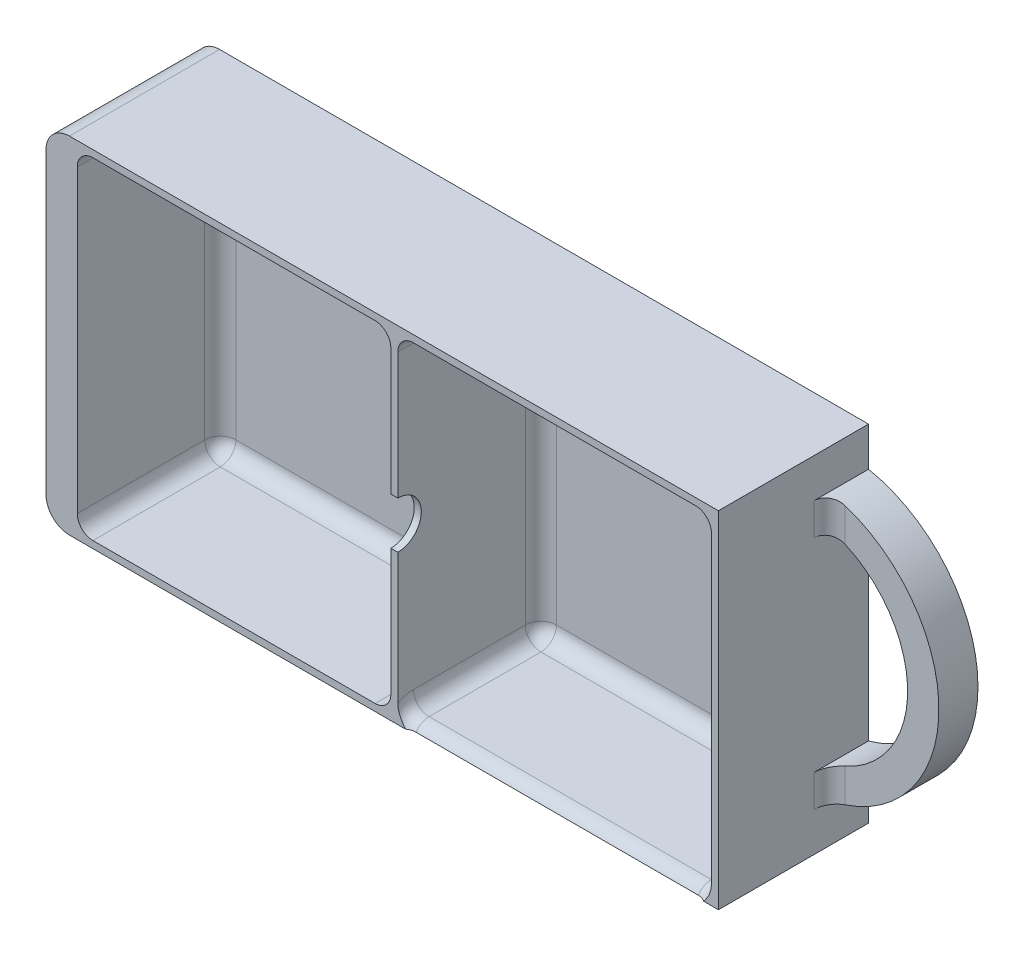
SolidWorks part; units mm, degrees
ref_plane "Спереди" through (0, 0, 0) normal (0, 0, 1) x (1, 0, 0)
ref_plane "Сверху" through (0, 0, 0) normal (0, 1, 0) x (1, 0, 0)
ref_plane "Справа" through (0, 0, 0) normal (1, 0, 0) x (0, 0, -1)
ref_plane "Плоскость4" through (0, 0, 9.6) normal (0, 0, 1) x (1, 0, 0)
sketch "Эскиз1" plane through (0, 0, 9.6) normal (0, 0, 1) x (1, 0, 0)
  line L0 (90, -22.1) -> (90, 22.1)
  line L1 (90, 22.1) -> (4, 22.1)
  line L2 (4, 22.1) -> (4, -22.1)
  line L3 (4, -22.1) -> (90, -22.1)
extrude "Бобышка-Вытянуть1" add sketch "Эскиз1" against normal blind 14.2
sketch "Эскиз2" plane through (0, 0, -4.6) normal (0, 0, -1) x (-1, 0, 0)
  line L0 (-90, -22.1) -> (-90, -17.1)
  line L1 (-90, 17.1) -> (-90, 22.1)
  line L2 (-90, 22.1) -> (-4, 22.1)
  line L3 (-4, 22.1) -> (-4, -22.1)
  line L4 (-4, -22.1) -> (-90, -22.1)
  line L5 (-90, -12.9948) -> (-90, 12.9948)
  arc A0 (-90, -17.1) -> (-90, 17.1) centre (-86.5568, 0) cw
  arc A1 (-90, 12.9948) -> (-90, -12.9948) centre (-86.5568, 0) ccw
extrude "Бобышка-Вытянуть2" add sketch "Эскиз2" along normal blind 5
sketch "Эскиз3" plane through (0, 0, 9.6) normal (0, 0, 1) x (1, 0, 0)
  line L0 (48.1, -21.2) -> (48.1, 21.2)
  line L1 (48.1, 21.2) -> (8, 21.2)
  line L2 (8, 21.2) -> (8, -21.2)
  line L3 (8, -21.2) -> (48.1, -21.2)
extrude "Вырез-Вытянуть1" cut sketch "Эскиз3" against normal blind 18.3
sketch "Эскиз4" plane through (0, 0, 9.6) normal (0, 0, 1) x (1, 0, 0)
  line L0 (49, 21.2) -> (49, -21.2)
  line L1 (49, -21.2) -> (89.1, -21.2)
  line L2 (89.1, -21.2) -> (89.1, 21.2)
  line L3 (89.1, 21.2) -> (49, 21.2)
extrude "Вырез-Вытянуть2" cut sketch "Эскиз4" against normal blind 18.3
hole_wizard "Диаметр отверстия Ø8.3 (8.3)1" positions "Эскиз6" profile "Эскиз5" hole size "Ø8.3" standard "Ansi Metric"
sketch "Эскиз6" plane through (4, 0, 0) normal (-1, 0, 0) x (0, 0, 1)
  point P0 (0, 0)
sketch "Эскиз5" plane through (4, 0, 0) normal (0, 1, 0) x (0, 0, 1)
  line L0 (0, 0) -> (0, 3.2)
  line L1 (0, 3.2) -> (4.15, 3.2)
  line L2 (4.15, 3.2) -> (4.15, 0)
  line L5 (4.15, 0) -> (0, 0)
  line L10 (0, 3.2) -> (-4.15, 3.2) construction
  line L11 (0, -6.35) -> (0, 107.95) construction
  dimension "Диаметр отверстия" = 8.3
  dimension "Глубина отверстия" = 3.2
  dimension "Угол заточки сверла" = 180
hole_wizard "Диаметр отверстия Ø6.0 (6)1" positions "Эскиз8" profile "Эскиз7" hole size "Ø6.0" standard "Ansi Metric"
sketch "Эскиз8" plane through (48.1, 0, 0) normal (-1, 0, 0) x (0, 0, 1)
  point P0 (9.6, 0)
sketch "Эскиз7" plane through (48.1, 0, 9.6) normal (0, 1, 0) x (0, 0, 1)
  line L0 (0, 0) -> (0, 0.9)
  line L1 (0, 0.9) -> (3, 0.9)
  line L2 (3, 0.9) -> (3, 0)
  line L5 (3, 0) -> (0, 0)
  line L11 (0, -6.35) -> (0, 107.95) construction
  dimension "Диаметр сквозного отверстия" = 6
  dimension "Глубина сквозного отверстия" = 0.9
fillet "Скругление1" radius 3 2 edges at (4, -22.1, 0) (4, 22.1, 0) tangent propagation no
sketch "Эскиз9" plane through (4, 0, 0) normal (-1, 0, 0) x (0, 0, 1)
  circle A0 centre (0, 0) radius 4.15 construction
  circle A1 centre (0, 0) radius 4.15
extrude "Бобышка-Вытянуть3" add sketch "Эскиз9" against normal blind 3.5
fillet "Скругление2" radius 2 12 edges at (69.05, -21.2, 9.6) (89.1, 0, -8.7) (69.05, 21.2, -8.7) (49, 21.2, 0.45) (48.1, -21.2, 0.45) (8, -21.2, 0.45) (8, 21.2, 0.45) (49, 0, -8.7) (48.1, 0, -8.7) (28.05, 21.2, -8.7) (28.05, -21.2, -8.7) (8, 0, -8.7)
fillet "Скругление3" radius 2 9 edges at (89.1, -21.4393, 8.5487) (89.1, -21.2, 0.45) (88.5142, -21.2, -8.1142) (69.05, -21.2, -8.7) (49.5858, -21.2, -8.1142) (49, -21.4393, 8.5487) (47.5142, 20.6142, -8.1142) (49, -21.2, 0.45) (48.1, 21.2, 1.45)
fillet "Скругление4" radius 2 2 edges at (88.5142, 20.6142, -8.1142) (89.1, 21.2, 1.45)
fillet "Скругление5" radius 2 2 edges at (90, -15.0474, -4.6) (90, 15.0474, -4.6)
